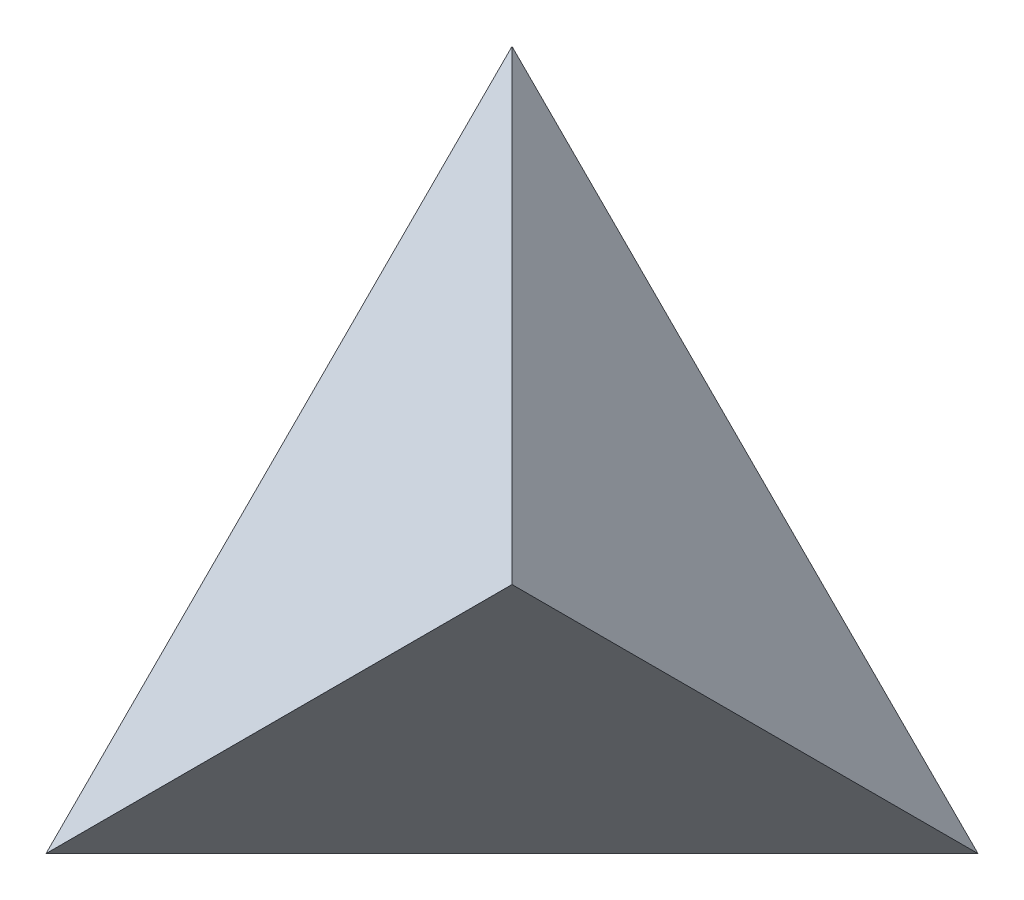
SolidWorks part; units mm, degrees
note: '?' marks a value the reader was unsure of.
ref_plane "Front Plane" through (0, 0, 0) normal (0, 0, 1) x (1, 0, 0)
ref_plane "Top Plane" through (0, 0, 0) normal (0, 1, 0) x (1, 0, 0)
ref_plane "Right Plane" through (0, 0, 0) normal (1, 0, 0) x (0, 0, -1)
sketch "Sketch8" plane through (0, 0, 0) normal (0, 1, 0) x (1, 0, 0)
  line L1 (-7.0711, -7.0711) -> (7.0711, -7.0711) construction
  line L2 (-7.0711, -7.0711) -> (-7.0711, 7.0711) construction
  line L3 (-7.0711, 7.0711) -> (7.0711, 7.0711) construction
  line L4 (7.0711, -7.0711) -> (7.0711, 7.0711) construction
  line L5 (-7.0711, -7.0711) -> (7.0711, 7.0711) construction
  line L6 (-7.0711, 7.0711) -> (7.0711, -7.0711) construction
  circle A0 centre (0, 0) radius 7.0711 construction
  point P0 (0, 0)
  dimension "side" = 20
ref_plane "Plane4" through (0, 0, 7.0711) normal (0, 0, 1) x (1, 0, 0)
sketch "Sketch9" plane through (0, 0, 7.0711) normal (0, 0, 1) x (1, 0, 0)
  line L0 (7.0711, 7.0711) -> (-7.0711, -7.0711) construction
  line L2 (7.0711, 7.0711) -> (7.0711, 0) construction
  line L3 (-7.0711, 0) -> (-7.0711, -7.0711) construction
  line L4 (-7.0711, 0) -> (7.0711, 0) construction
  point P2 (0, 0)
  dimension "side" = 20
ref_plane "Plane5" through (0, 0, -7.0711) normal (0, 0, 1) x (1, 0, 0)
sketch "Sketch10" plane through (0, 0, -7.0711) normal (0, 0, 1) x (1, 0, 0)
  line L0 (7.0711, -7.0711) -> (-7.0711, 7.0711) construction
  line L1 (-7.0711, 0) -> (-7.0711, 7.0711) construction
  line L3 (-7.0711, 0) -> (7.0711, 0) construction
  point P2 (0, 0)
  dimension "side" = 20
ref_plane "Plane7" through (2.357, 2.357, -2.357) normal (-0.5774, -0.5774, 0.5774) x (0.4082, 0.4082, 0.8165)
sketch "Sketch11" plane through (2.357, 2.357, -2.357) normal (-0.5774, -0.5774, 0.5774) x (0.4082, 0.4082, 0.8165)
  line L0 (-5.7735, -10) -> (-5.7735, 10) construction
  line L1 (-5.7735, -10) -> (11.547, 0)
  line L2 (11.547, 0) -> (-5.7735, 10)
  line L3 (-5.7735, 10) -> (-5.7735, -10)
  circle A0 centre (0, 0) radius 5.7735 construction
surface "Surface-Plane3" sketch "Sketch11"
ref_plane "Plane8" through (-2.357, -2.357, -2.357) normal (0.5774, 0.5774, 0.5774) x (0.4082, 0.4082, -0.8165)
sketch "Sketch12" plane through (-2.357, -2.357, -2.357) normal (0.5774, 0.5774, 0.5774) x (0.4082, 0.4082, -0.8165)
  line L0 (5.7735, -10) -> (5.7735, 10) construction
  line L1 (-11.547, 0) -> (5.7735, -10)
  line L2 (5.7735, -10) -> (5.7735, 10)
  line L3 (5.7735, 10) -> (-11.547, 0)
  circle A0 centre (0, 0) radius 5.7735 construction
surface "Surface-Plane4" sketch "Sketch12"
ref_axis "Axis1" through (0, 0, 0) along (0, 1, 0)?
pattern_circular "CirPattern2" count 2 over 360 about axis through (0, 0, 0) along (0, 1, 0)
surface "Surface-Knit2"
